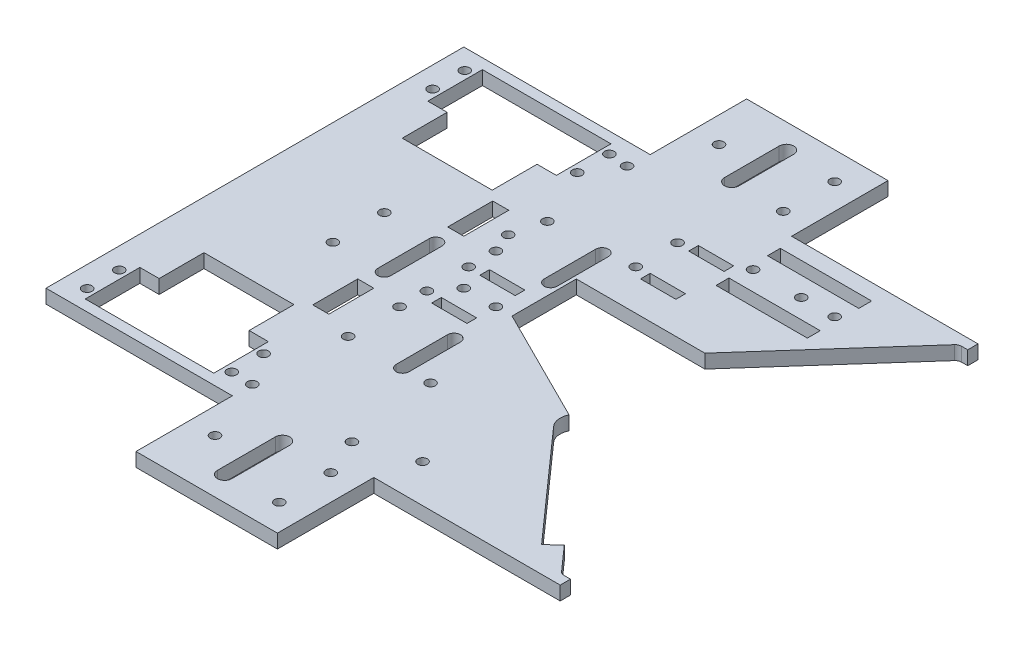
SolidWorks part; units mm, degrees
material "Acrylic (Medium-high impact)"
ref_plane "Front Plane" through (0, 0, 0) normal (0, 0, 1) x (1, 0, 0)
ref_plane "Top Plane" through (0, 0, 0) normal (0, 1, 0) x (1, 0, 0)
ref_plane "Right Plane" through (0, 0, 0) normal (1, 0, 0) x (0, 0, -1)
sketch "Sketch2" plane through (0, 0, 0) normal (0, 1, 0) x (1, 0, 0)
  line L2 (0, 0) -> (0, 65)
  line L3 (0, 65) -> (58, 65)
  line L4 (160, 0) -> (160, 65)
  line L8 (0, 0) -> (160, 0)
  line L9 (102, 65) -> (160, 65)
  line L11 (102, 65) -> (102, 95)
  line L12 (58, 65) -> (58, 95)
  line L13 (58, 95) -> (102, 95)
  dimension "D1" = 65
  dimension "D2" = 160
  dimension "D3" = 44
  dimension "D4" = 30
extrude "Boss-Extrude1" add sketch "Sketch2" along normal blind 4.3
mirror "Mirror1" about plane through (0, 4.3, 0) normal (0, 0, -1) of bodies 101
sketch "Sketch3" plane through (0, 4.3, 0) normal (0, 1, 0) x (1, 0, 0)
  line L0 (160, 61.8) -> (160, -61.8)
  line L1 (120.0126, 20) -> (157.1565, 61.8)
  line L3 (80.0126, 0) -> (80.0126, 20)
  line L4 (80.0126, 20) -> (120.0126, 20)
  line L12 (160, 65) -> (102, 65)
  line L13 (102, 65) -> (102, 95)
  line L15 (102, 95) -> (58, 95)
  line L16 (58, 65) -> (0, 65)
  line L17 (0, 65) -> (0, -65)
  line L18 (0, -65) -> (58, -65)
  line L20 (58, 95) -> (58, 65)
  line L22 (102, -65) -> (160, -65)
  line L23 (160, -65) -> (160, 65)
  line L36 (58, -65) -> (58, -95)
  line L38 (58, -95) -> (102, -95)
  line L39 (58, -95) -> (102, -95)
  line L40 (102, -95) -> (102, -65)
  line L42 (160, -61.8) -> (157.1556, -61.8)
  line L45 (160, 61.8) -> (157.1565, 61.8)
  line L48 (80.0126, 0) -> (120, -20)
  line L49 (120, -20) -> (157.1556, -61.8)
  line M24 (160, -65) -> (160, 65)
  dimension "D2" = 130
  dimension "D3" = 20
  dimension "D4" = 40
  dimension "D1" = 0
extrude "Cut-Extrude1" cut sketch "Sketch3" against normal blind 4.5 contours L48 L49 L1 L4 L3 M24 region at (132.7054, 4.3, -1.1594)
fillet "Fillet1" radius 2 2 edges at (157.1565, 2.15, -61.8) (157.1556, 2.15, 61.8)
ref_axis "Axis1" through (80, 4.3, 95) along (0, 0, -1)
sketch "Sketch4" plane through (0, 4.3, 0) normal (0, 1, 0) x (1, 0, 0)
  line L0 (80, -95) -> (80, 95)
  line L1 (102, -95) -> (58, -95) construction
  line L2 (102, 95) -> (58, 95) construction
ref_plane "Plane2" through (0, 4.3, 0) normal (0, 1, 0) x (1, 0, 0)
sketch "Sketch6" plane through (0, 4.3, 0) normal (0, 1, 0) x (1, 0, 0)
  line L3 (9, -61.8) -> (49, -61.8)
  line L6 (29, -45.8) -> (29, -44.8)
  line L7 (9, -44.8) -> (15, -44.8)
  line L11 (43, -44.8) -> (43, -30.8418)
  line L12 (15, -44.8) -> (15, -30.8418)
  line L13 (15, -30.8418) -> (43, -30.8418)
  line L15 (0, 0) -> (80.0126, 0)
  line L16 (80.0126, 0) -> (120, -20) construction
  line L18 (9, 44.8) -> (15, 44.8)
  line L20 (15, 30.8418) -> (43, 30.8418)
  line L21 (15, 44.8) -> (15, 30.8418)
  line L22 (43, 44.8) -> (43, 30.8418)
  line L25 (15, -45.8) -> (15, -30.8418) construction
  line L27 (9, 61.8) -> (49, 61.8)
  line L30 (4, -61.8) -> (3, -61.8)
  line L31 (0, -61.8) -> (160, -61.8) construction
  line L32 (3, -61.8) -> (4, -61.8)
  line L33 (3, -44.8) -> (3, -62.8) construction
  line L34 (3, -62.8) -> (55, -62.8) construction
  line L35 (55, -44.8) -> (55, -62.8) construction
  line L36 (4, -61.8) -> (54, -61.8) construction
  line L37 (0, 61.8) -> (160, 61.8) construction
  line L38 (54, 61.8) -> (55, 61.8)
  line L39 (54, 61.8) -> (55, 61.8)
  line L40 (43, 44.8) -> (49, 44.8)
  line L41 (4, -45.8) -> (4, -61.8) construction
  line L42 (4, -45.8) -> (54, -45.8) construction
  line L43 (43, -44.8) -> (49, -44.8)
  line L44 (3, -44.8) -> (55, -44.8) construction
  line L45 (29, -45.8) -> (29, -30.8418) construction
  line L46 (43, -45.8) -> (43, -30.8418) construction
  line L47 (54, -45.8) -> (54, -61.8) construction
  line L48 (9, -61.8) -> (49, -61.8)
  line L52 (9, 61.8) -> (9, 44.8)
  line L53 (55, 61.8) -> (54, 61.8)
  line L56 (49, 61.8) -> (49, 44.8)
  line L59 (3, -61.8) -> (4, -61.8)
  line L60 (9, -44.8) -> (9, -61.8)
  line L64 (49, -44.8) -> (49, -61.8)
  dimension "D4" = 1
  dimension "D5" = 14
  dimension "D6" = 14
extrude "Cut-Extrude2" cut sketch "Sketch6" against normal blind 10
sketch "Sketch8" plane through (0, 4.3, 0) normal (0, 1, 0) x (1, 0, 0)
  circle A0 centre (6.5, 58.8) radius 1.5
  circle A1 centre (6.5, 48.8) radius 1.5
  circle A2 centre (51.5, 48.8) radius 1.5
  circle A3 centre (51.5, 58.8) radius 1.5
  circle A4 centre (6.5, -48.7) radius 1.5
  circle A5 centre (6.5, -58.7) radius 1.5
  circle A6 centre (51.5, -58.7) radius 1.5
  circle A7 centre (51.5, -48.8) radius 1.5
  dimension "D7" = 3
extrude "Cut-Extrude3" cut sketch "Sketch8" against normal blind 10
sketch "Sketch9" plane through (0, 0, 0) normal (0, -1, 0) x (1, 0, 0)
  line L0 (75.75, 69.4) -> (75.75, 87.4)
  line L1 (75.75, -87.4) -> (75.75, -70.4)
  line L2 (80.25, -87.4) -> (80.25, -70.4)
  line L4 (80.25, 69.4) -> (80.25, 87.4)
  circle A0 centre (94, 70.4) radius 1.5
  circle A1 centre (66, 78.4) radius 1.5
  circle A2 centre (66, -78.4) radius 1.5
  circle A3 centre (94, -86.4) radius 1.5
  circle A4 centre (94, 86.4) radius 1.5
  circle A5 centre (94, -70.4) radius 1.5
  arc A6 (75.75, -87.4) -> (80.25, -87.4) centre (78, -87.4) ccw
  arc A7 (80.25, -70.4) -> (75.75, -70.4) centre (78, -70.4) ccw
  arc A10 (75.75, 69.4) -> (80.25, 69.4) centre (78, 69.4) ccw
  arc A12 (80.25, 87.4) -> (75.75, 87.4) centre (78, 87.4) ccw
  dimension "D1" = 3
extrude "Cut-Extrude4" cut sketch "Sketch9" against normal blind 10
sketch "Sketch7" plane through (0, 4.3, 0) normal (0, 1, 0) x (1, 0, 0)
  line L0 (0, 0) -> (80.0126, 0)
  line L1 (0, 65) -> (0, -65) construction
  line L2 (80.0126, 0) -> (80.0126, 20) construction
  line L3 (80, -95) -> (80, 95) construction
  line L4 (64, -9) -> (75, -9)
  line L5 (64, -6) -> (75, -6)
  line L6 (64, -9) -> (64, -6)
  line L7 (75, -9) -> (75, -6)
  line L8 (64, -7.5) -> (75, -7.5)
  line L9 (64, 7.5) -> (75, 7.5)
  line L10 (75, 9) -> (75, 6)
  line L11 (64, 9) -> (64, 6)
  line L12 (64, 6) -> (75, 6)
  line L13 (64, 9) -> (75, 9)
  line L14 (89.9874, 30) -> (100.9874, 30)
  line L15 (89.9874, 33) -> (100.9874, 33)
  line L16 (89.9874, 30) -> (89.9874, 33)
  line L17 (100.9874, 30) -> (100.9874, 33)
  line L20 (100.9874, 48) -> (100.9874, 45)
  line L21 (89.9874, 48) -> (89.9874, 45)
  line L22 (89.9874, 45) -> (100.9874, 45)
  line L23 (89.9874, 48) -> (100.9874, 48)
  line L24 (80.0126, 20) -> (120.0126, 20) construction
  circle A0 centre (60.0126, -6.5) radius 1.5
  circle A1 centre (60.0126, 6.5) radius 1.5
  circle A2 centre (86, 32.5) radius 1.5
  circle A3 centre (86, 45.5) radius 1.5
  dimension "D1" = 3
  dimension "D8" = 3
  dimension "D2" = 6.5
  dimension "D3" = 20
  dimension "D6" = 11
  dimension "D4" = 5
  dimension "D5" = 3
  dimension "D7" = 7.5
  dimension "D9" = 11
  dimension "D10" = 3
  dimension "D11" = 12
  dimension "D12" = 13
  dimension "D13" = 10
  dimension "D14" = 3.9874
  dimension "D15" = 0.5
  dimension "D16" = 0.5
  dimension "D17" = 3.9874
  dimension "D18" = 6
  dimension "D19" = 11
sketch "Sketch10" plane through (0, 4.3, 0) normal (0, 1, 0) x (1, 0, 0)
  line L0 (120, -20) -> (156.5589, -61.1287) construction
  line L1 (123.3218, -23.737) -> (149.8964, -53.6334)
  line L2 (116.263, -23.3218) -> (146.1593, -56.9552)
  line L3 (149.8964, -53.6334) -> (146.1593, -56.9552)
  line L4 (120, -20) -> (156.5589, -61.1287) construction
  line L5 (116.263, -23.3218) -> (152.8218, -64.4505) construction
  arc A0 (123.3218, -23.737) -> (116.263, -23.3218) centre (120, -20) ccw
  point P12 (0, 0)
  dimension "D1" = 5
  dimension "D2" = 45
extrude "Cut-Extrude5" cut sketch "Sketch10" against normal blind 10
sketch "Sketch11" plane through (0, 0, 0) normal (0, -1, 0) x (1, 0, 0)
  line L0 (0, 0) -> (80.0126, 0) construction
  line L1 (80, 95) -> (80, -95) construction
  line L2 (80.0126, 0) -> (0, 0)
  line L4 (75, 31.0313) -> (75, 15.0313)
  line L6 (79, 31.0313) -> (79, 15.0313)
  line L7 (79, -31.0313) -> (79, -15.0313)
  line L8 (75, -31.0313) -> (75, -15.0313)
  circle A0 centre (60, 31) radius 1.5
  circle A1 centre (60, 15) radius 1.5
  arc A2 (75, 31.0313) -> (79, 31.0313) centre (77, 31.0313) cw
  arc A3 (75, 15.0313) -> (79, 15.0313) centre (77, 15.0313) ccw
  arc A4 (75, -15.0313) -> (79, -15.0313) centre (77, -15.0313) cw
  arc A5 (75, -31.0313) -> (79, -31.0313) centre (77, -31.0313) ccw
  circle A6 centre (60, -15) radius 1.5
  circle A7 centre (60, -31) radius 1.5
  dimension "D1" = 3
  dimension "D2" = 16
  dimension "D3" = 15
  dimension "D4" = 20
  dimension "D5" = 15
  dimension "D6" = 4
extrude "Cut-Extrude6" cut sketch "Sketch11" against normal blind 10 contours L4 A3 L6 A2 | L8 A5 L7 A4 | A7 | A0 | A1 | A6 region at (77, 0, 23.0313) region at (77, 0, -23.0313) region at (60, 0, -31)
sketch "Sketch12" plane through (0, 0, 0) normal (0, -1, 0) x (-1, 0, 0)
  line L0 (0, 0) -> (-80.0126, 0) construction
  line L3 (-50.2627, -8) -> (-50.2627, 8)
  line L4 (-50.2627, 0) -> (-46.2627, 0)
  line L5 (-46.2627, -8) -> (-46.2627, 8)
  line L6 (0, 0) -> (-46.2627, 0)
  line L7 (0, 65) -> (0, -65) construction
  line L8 (-160, -61.8) -> (0, -61.8) construction
  line L9 (-80.0126, 0) -> (-50.2627, 0)
  line L10 (-80.0126, 0) -> (-115.5281, -17.7634) construction
  line L11 (-80.0126, 0) -> (-80.0126, 20) construction
  line L12 (-58, -65) -> (0, -65) construction
  line L13 (-58, 65) -> (0, 65) construction
  circle A0 centre (-32.2627, -8) radius 1.5
  circle A1 centre (-32.2627, 8) radius 1.5
  arc A2 (-46.2627, 8) -> (-50.2627, 8) centre (-48.2627, 8) ccw
  arc A3 (-50.2627, -8) -> (-46.2627, -8) centre (-48.2627, -8) ccw
  circle A5 centre (-32.2627, -8) radius 1.5 construction
  circle A6 centre (-32.2627, 8) radius 1.5 construction
  dimension "D1" = 3
  dimension "D8" = 8
  dimension "D9" = 8
  dimension "D2" = 8
  dimension "D3" = 14
  dimension "D4" = 4
  dimension "D5" = 61.8
  dimension "D6" = 65
  dimension "D7" = 65
extrude "Cut-Extrude7" cut sketch "Sketch12" against normal blind 10 contours A3 L5 L4 L3 | L4 L5 A2 L3 | A0 | A1 region at (48.2627, 0, 4.7958) region at (48.2627, 0, -4.7958) region at (32.2627, 0, 8) region at (32.2627, 0, -8)
extrude "Cut-Extrude8" cut sketch "Sketch7" against normal blind 9 contours A0 | L4 L7 L5 L6 | L12 L10 L13 L11 | A1 | L23 L20 L22 L21 | L15 L17 L14 L16 | A3 | A2
sketch "Sketch13" plane through (0, 4.3, 0) normal (0, 1, 0) x (1, 0, 0)
  line L0 (80.0126, 0) -> (59.0194, 0)
  line L1 (80, -95) -> (80, 95) construction
  circle A0 centre (65, 0) radius 1.5
  circle A1 centre (75, 0) radius 1.5
  dimension "D2" = 3
  dimension "D3" = 5
  dimension "D1" = 10
extrude "Cut-Extrude9" cut sketch "Sketch13" against normal blind 10 contours L0 A0 | L0 A0 | L0 A1 | L0 A1 region at (75, 4.3, 0.6366) region at (75, 4.3, -0.6366) region at (65, 4.3, 0.6366) region at (65, 4.3, -0.6366)
sketch "Sketch14" plane through (0, 4.3, 0) normal (0, 1, 0) x (1, 0, 0)
  circle A0 centre (57.5, 58.3) radius 1.5
  circle A2 centre (57.5, 21.3) radius 1.5
  circle A3 centre (85.37, -30.7129) radius 1.5
  circle A4 centre (105.301, -53.1351) radius 1.5
  dimension "D1" = 3
  dimension "D2" = 3
extrude "Cut-Extrude10" cut sketch "Sketch14" against normal blind 10
sketch "Sketch15" plane through (0, 4.3, 0) normal (0, 1, 0) x (1, 0, 0)
  line L1 (46, 28) -> (51, 28)
  line L2 (46, 28) -> (46, 14)
  line L3 (46, 14) -> (51, 14)
  line L4 (51, 28) -> (51, 14)
  line L6 (0, 65) -> (0, -65) construction
  line L7 (80.0126, 0) -> (53.7017, 0)
  line L8 (46, -14) -> (51, -14)
  line L9 (51, -28) -> (51, -14)
  line L10 (46, -28) -> (51, -28)
  line L11 (46, -28) -> (46, -14)
  arc A0 (50.2627, 8) -> (46.2627, 8) centre (48.2627, 8) ccw construction
  arc A1 (46.2627, -8) -> (50.2627, -8) centre (48.2627, -8) ccw construction
  dimension "D1" = 46
  dimension "D2" = 5
  dimension "D3" = 14
  dimension "D4" = 14
  dimension "D5" = 14
  dimension "D6" = 6
  dimension "D7" = 6
extrude "Cut-Extrude11" cut sketch "Sketch15" against normal blind 10 contours L4 L1 L2 L3 | L11 L10 L9 L8 region at (48.5, 4.3, -21) region at (48.5, 4.3, 21)
sketch "Sketch16" plane through (0, 4.3, 0) normal (0, 1, 0) x (1, 0, 0)
  circle A0 centre (89, -58.8) radius 1.5
  circle A1 centre (58, -58.8) radius 1.5
  dimension "D1" = 3
extrude "Cut-Extrude12" cut sketch "Sketch16" against normal blind 10
ref_plane "Plane3" through (44.2426, 0, 0) normal (1, 0, 0) x (0, 0, -1)
sketch "Sketch17" plane through (44.2426, 0, 0) normal (1, 0, 0) x (0, 0, -1)
  line L4 (0, 0) -> (20, 0)
  line L5 (20, 0) -> (20, 4.3)
  line L6 (20, 4.3) -> (0, 4.3)
  line L7 (0, 4.3) -> (0, 0)
  line L8 (0, 0) -> (20, 0)
  line L9 (20, 0) -> (20, 4.3)
  line L10 (20, 4.3) -> (0, 4.3)
  line L11 (0, 4.3) -> (0, 0)
  circle A0 centre (-2.83, 16.28) radius 0.5
  point P6 (0, 2.15)
  dimension "D4" = 1
  dimension "D2" = 2.83
  dimension "D3" = 14.13
  dimension "D1" = 0
sketch "Sketch18" plane through (0, 4.3, 0) normal (0, 1, 0) x (1, 0, 0)
  line L0 (121.5, 50) -> (128.9, 50)
  line L1 (103.5, 60) -> (131.9, 60)
  line L2 (102, 65) -> (102, 95) construction
  line L3 (160, 65) -> (102, 65) construction
  line L4 (103.5, 60) -> (103.5, 56)
  line L5 (106.5, 50) -> (118.5, 50)
  line L6 (131.9, 60) -> (131.9, 56)
  line L7 (103.5, 60) -> (131.9, 60)
  line L8 (103.5, 60) -> (103.5, 56)
  line L9 (103.5, 56) -> (131.9, 56)
  line L10 (131.9, 60) -> (131.9, 56)
  line L11 (103.5, 44) -> (131.9, 44)
  line L12 (131.9, 40) -> (131.9, 44)
  line L13 (103.5, 40) -> (131.9, 40)
  line L14 (103.5, 40) -> (103.5, 44)
  circle A0 centre (105, 50) radius 1.5
  circle A1 centre (120, 50) radius 1.5
  circle A3 centre (130.4, 50) radius 1.5
  dimension "D1" = 3
  dimension "D6" = 3
  dimension "D2" = 15
  dimension "D4" = 3
  dimension "D5" = 15
  dimension "D7" = 25.4
  dimension "D8" = 4
  dimension "D9" = 6
extrude "Cut-Extrude13" cut sketch "Sketch18" against normal blind 10 contours L4 L9 L6 L1 | A0 | A1 | A3 | L14 L13 L12 L11 region at (130.4, 4.3, -50) region at (120, 4.3, -50) region at (105, 4.3, -50) region at (117.7, 4.3, -58) region at (117.7, 4.3, -42)
